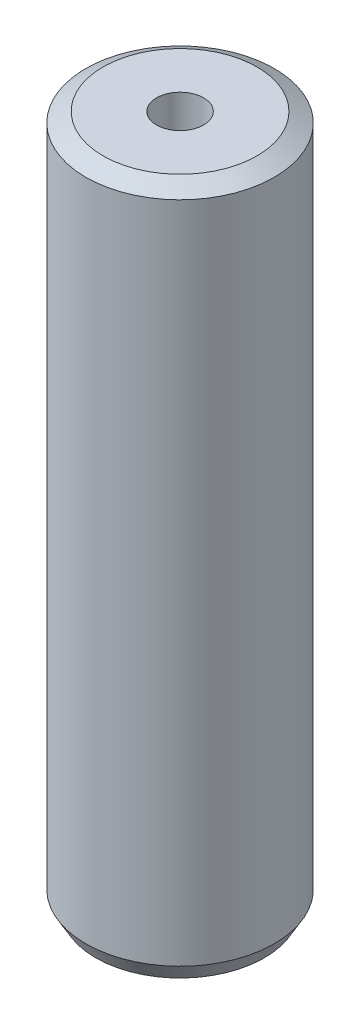
SolidWorks part; units mm, degrees
ref_plane "Front Plane" through (0, 0, 0) normal (0, 0, 1) x (1, 0, 0)
ref_plane "Top Plane" through (0, 0, 0) normal (0, 1, 0) x (1, 0, 0)
ref_plane "Right Plane" through (0, 0, 0) normal (1, 0, 0) x (0, 0, -1)
sketch "Sketch1" plane through (0, 0, 0) normal (0, 1, 0) x (1, 0, 0)
  circle A0 centre (0, 0) radius 10
  dimension "SHAFT_OD" = 20
extrude "Boss-Extrude1" add sketch "Sketch1" along normal blind 73.3156
sketch "Sketch2" plane through (0, 0, 0) normal (0, 1, 0) x (1, 0, 0)
  circle A0 centre (0, 0) radius 2.4985
  dimension "BORE_D" = 4.9969
extrude "Cut-Extrude1" cut sketch "Sketch2" along normal through all
chamfer "Chamfer1" distance 1.0547 angle 60 2 edges at (0, 73.3156, 10) (0, 0, 10) first distance on face at (0, 73.3156, 10) first distance on face at (0, 0, 2.4985)
